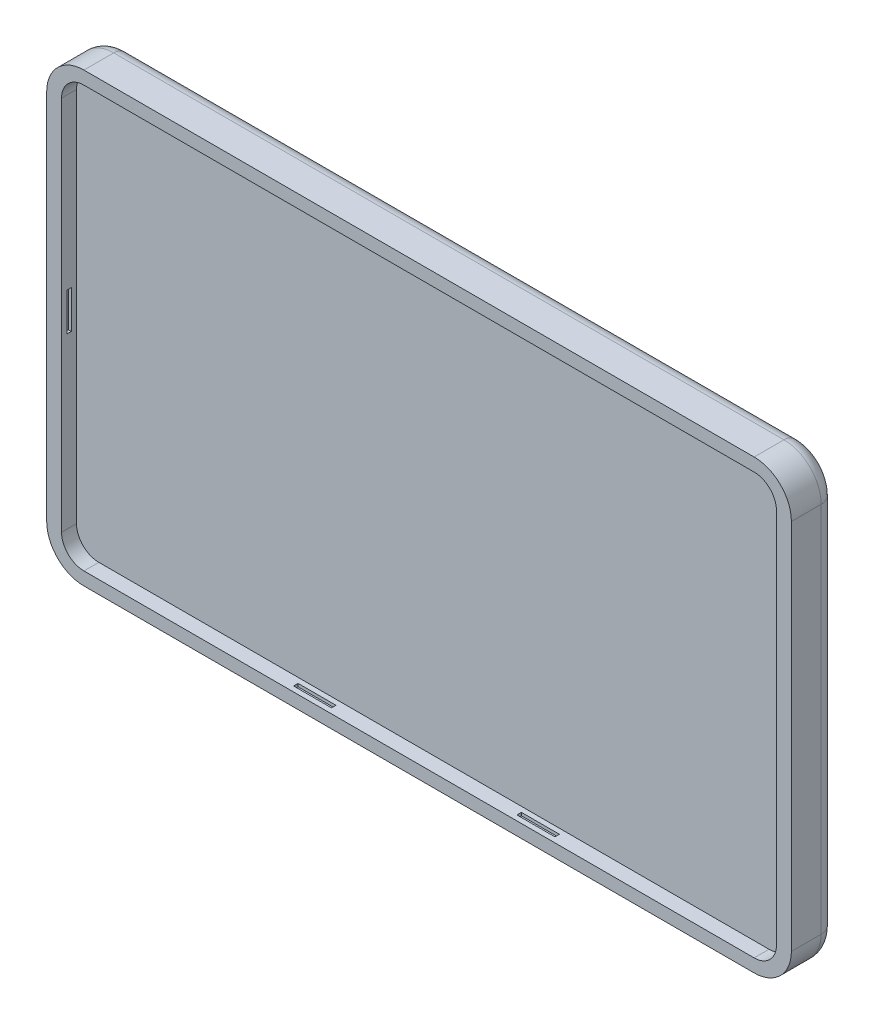
SolidWorks part; units mm, degrees
ref_plane "前视基准面" through (0, 0, 0) normal (0, 0, 1) x (1, 0, 0)
ref_plane "上视基准面" through (0, 0, 0) normal (0, 1, 0) x (1, 0, 0)
ref_plane "右视基准面" through (0, 0, 0) normal (1, 0, 0) x (0, 0, -1)
other "Configuration Table"
sketch "草图1" plane through (0, 0, 0) normal (0, 0, 1) x (1, 0, 0)
  line L1 (50, 30) -> (-50, 30)
  line L2 (50, 30) -> (50, -30)
  line L3 (50, -30) -> (-50, -30)
  line L4 (-50, 30) -> (-50, -30)
  line L5 (50, 30) -> (-50, -30) construction
  line L6 (50, -30) -> (-50, 30) construction
  point P0 (0, 0)
  dimension "D1" = 100
  dimension "D2" = 60
extrude "凸台-拉伸1" add sketch "草图1" along normal blind 6
fillet "圆角1" radius 5 4 edges at (-50, -30, 3) (50, -30, 3) (50, 30, 3) (-50, 30, 3)
fillet "圆角2" radius 2 8 edges at (48.5355, -28.5355, 0) (50, 0, 0) (48.5355, 28.5355, 0) (0, 30, 0) (-48.5355, 28.5355, 0) (-50, 0, 0) (-48.5355, -28.5355, 0) (0, -30, 0)
sketch "草图2" plane through (0, 0, 6) normal (0, 0, 1) x (1, 0, 0)
  line L1 (-45, 28.25) -> (45, 28.25)
  line L2 (-48, 25.25) -> (-48, -25.25)
  line L3 (-45, -28.25) -> (45, -28.25)
  line L4 (48, 25.25) -> (48, -25.25)
  line L5 (-48, 28.25) -> (48, -28.25) construction
  line L6 (-48, -28.25) -> (48, 28.25) construction
  arc A0 (45, -28.25) -> (48, -25.25) centre (45, -25.25) ccw
  arc A1 (48, 25.25) -> (45, 28.25) centre (45, 25.25) ccw
  arc A2 (-45, 28.25) -> (-48, 25.25) centre (-45, 25.25) ccw
  arc A3 (-45, -28.25) -> (-48, -25.25) centre (-45, -25.25) cw
  point P0 (0, 0)
  dimension "D1" = 3
  dimension "D2" = 96
  dimension "D3" = 56.5
extrude "切除-拉伸1" cut sketch "草图2" against normal blind 2
sketch "草图4" plane through (0, -28.25, 0) normal (0, 1, 0) x (1, 0, 0)
  line L0 (45, -5) -> (-45, -5) construction
  line L1 (17.55, -5.3) -> (12.45, -5.3)
  line L2 (17.55, -5.3) -> (17.55, -4.7)
  line L3 (17.55, -4.7) -> (12.45, -4.7)
  line L4 (12.45, -5.3) -> (12.45, -4.7)
  line L5 (17.55, -5.3) -> (12.45, -4.7) construction
  line L6 (17.55, -4.7) -> (12.45, -5.3) construction
  line L10 (-12.45, -5.3) -> (-17.55, -5.3)
  line L11 (-12.45, -5.3) -> (-12.45, -4.7)
  line L12 (-12.45, -4.7) -> (-17.55, -4.7)
  line L13 (-17.55, -5.3) -> (-17.55, -4.7)
  line L14 (-12.45, -5.3) -> (-17.55, -4.7) construction
  line L15 (-12.45, -4.7) -> (-17.55, -5.3) construction
  line L16 (45, -6) -> (45, -2) construction
  line L17 (-45, -2) -> (-45, -6) construction
  line L18 (45, -6) -> (-45, -6) construction
  point P0 (15, -5)
  point P12 (-15, -5)
  dimension "D1" = 1
  dimension "D2" = 0.6
  dimension "D3" = 5.1
  dimension "D4" = 0.6
  dimension "D5" = 5.1
  dimension "D6" = 30
  dimension "D7" = 60
extrude "切除-拉伸2" cut sketch "草图4" against normal blind 0.4
sketch "草图5" plane through (0, 28.25, 0) normal (0, -1, 0) x (1, 0, 0)
  line L0 (-17.55, 5.3) -> (-17.55, 4.7) construction
  line L1 (-12.45, 5.3) -> (-17.55, 5.3) construction
  line L2 (-12.45, 4.7) -> (-17.55, 4.7) construction
  line L3 (-12.45, 5.3) -> (-12.45, 4.7) construction
  line L4 (12.45, 5.3) -> (12.45, 4.7) construction
  line L5 (17.55, 5.3) -> (12.45, 5.3) construction
  line L6 (17.55, 5.3) -> (17.55, 4.7) construction
  line L7 (17.55, 4.7) -> (12.45, 4.7) construction
  line L8 (-17.55, 5.3) -> (-17.55, 4.7)
  line L9 (-12.45, 5.3) -> (-17.55, 5.3)
  line L10 (-12.45, 4.7) -> (-17.55, 4.7)
  line L11 (-12.45, 5.3) -> (-12.45, 4.7)
  line L12 (12.45, 5.3) -> (12.45, 4.7)
  line L13 (17.55, 5.3) -> (12.45, 5.3)
  line L14 (17.55, 5.3) -> (17.55, 4.7)
  line L15 (17.55, 4.7) -> (12.45, 4.7)
extrude "切除-拉伸3" cut sketch "草图5" against normal blind 0.4
sketch "草图6" plane through (-48, 0, 0) normal (1, 0, 0) x (0, 0, -1)
  line L0 (-6, -25) -> (-2, -25) construction
  line L1 (-5, -25) -> (-5, 25) construction
  line L2 (-2, 25) -> (-6, 25) construction
  line L3 (-6, -25) -> (-6, 25) construction
  line L5 (-5.3, -2.55) -> (-4.7, -2.55)
  line L6 (-5.3, -2.55) -> (-5.3, 2.55)
  line L7 (-5.3, 2.55) -> (-4.7, 2.55)
  line L8 (-4.7, -2.55) -> (-4.7, 2.55)
  line L9 (-5.3, -2.55) -> (-4.7, 2.55) construction
  line L10 (-5.3, 2.55) -> (-4.7, -2.55) construction
  point P8 (-5, 0)
  point P15 (-5, 0)
  dimension "D1" = 1
  dimension "D2" = 5.1
  dimension "D3" = 0.6
extrude "切除-拉伸4" cut sketch "草图6" against normal blind 0.4
sketch "草图7" plane through (48, 0, 0) normal (-1, 0, 0) x (0, 0, 1)
  line L0 (5.3, 2.55) -> (4.7, 2.55) construction
  line L1 (5.3, -2.55) -> (4.7, -2.55) construction
  line L2 (5.3, -2.55) -> (5.3, 2.55) construction
  line L3 (4.7, -2.55) -> (4.7, 2.55) construction
  line L4 (5.3, 2.55) -> (4.7, 2.55)
  line L5 (5.3, -2.55) -> (4.7, -2.55)
  line L6 (5.3, -2.55) -> (5.3, 2.55)
  line L7 (4.7, -2.55) -> (4.7, 2.55)
extrude "切除-拉伸5" cut sketch "草图7" against normal blind 0.4
